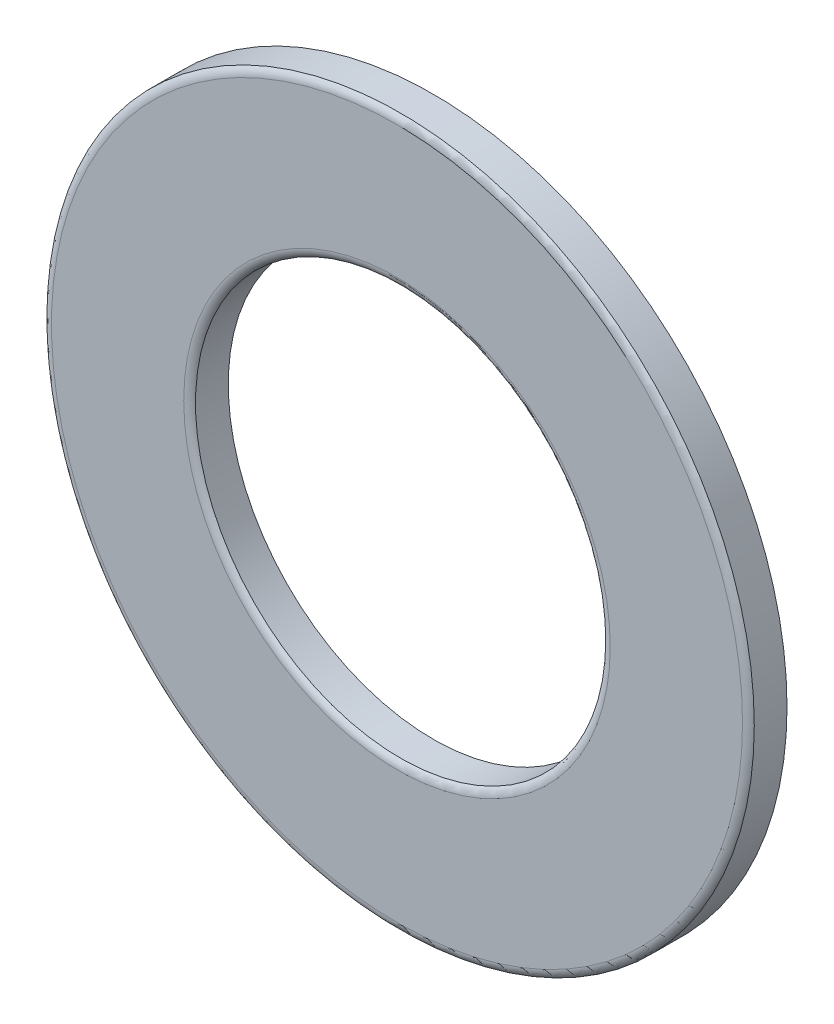
SolidWorks part; units mm, degrees
ref_plane "Front Plane" through (0, 0, 0) normal (0, 0, 1) x (1, 0, 0)
ref_plane "Top Plane" through (0, 0, 0) normal (0, 1, 0) x (1, 0, 0)
ref_plane "Right Plane" through (0, 0, 0) normal (1, 0, 0) x (0, 0, -1)
sketch "Sketch1" plane through (0, 0, 0) normal (0, 0, 1) x (1, 0, 0)
  circle A0 centre (0, 0) radius 22.225
  circle A1 centre (0, 0) radius 12.8905
  point P4 (12.8905, 0)
  dimension "ID" = 25.781
  dimension "OD" = 44.45
sketch "Sketch2" plane through (0, 0, 0) normal (1, 0, 0) x (0, 0, -1)
  line L0 (-1.143, 22.225) -> (1.143, 22.225)
  line L1 (0, 22.225) -> (0, 19.939) construction
  point P3 (0, 22.225)
  point P5 (-1.1938, 22.225)
  point P6 (-1.0922, 22.225)
  point P7 (1.0922, 22.225)
  point P8 (1.1938, 22.225)
  dimension "Thickness Range" = 2.286
  dimension "Thickness Range Max" = 2.3876
  dimension "Thickness Range Min" = 2.1844
sketch "Sketch3" plane through (0, 0, 0) normal (0, 0, 1) x (1, 0, 0)
  circle A0 centre (0, 0) radius 12.8905 construction
  circle A1 centre (0, 0) radius 22.225 construction
  circle A2 centre (0, 0) radius 12.8905
  circle A3 centre (0, 0) radius 22.225
extrude "Boss-Extrude1" add sketch "Sketch3" along normal up to vertex (1.143 mm away) from vertex at -1.143 starting at point (0, 22.225, -1.143)
chamfer "Chamfer1" distance 0.2286 angle 30 2 edges at (22.225, 0, 1.143) (12.8905, 0, 1.143)
fillet "Fillet1" radius 0.6858 2 edges at (13.0225, 0, 1.143) (22.093, 0, 1.143)
equation "\"D1@Fillet1\"=\"D1@Chamfer1\"*3"
equation "\"D1@Chamfer1\"=\"Thickness Range@Sketch2\"*.1"
